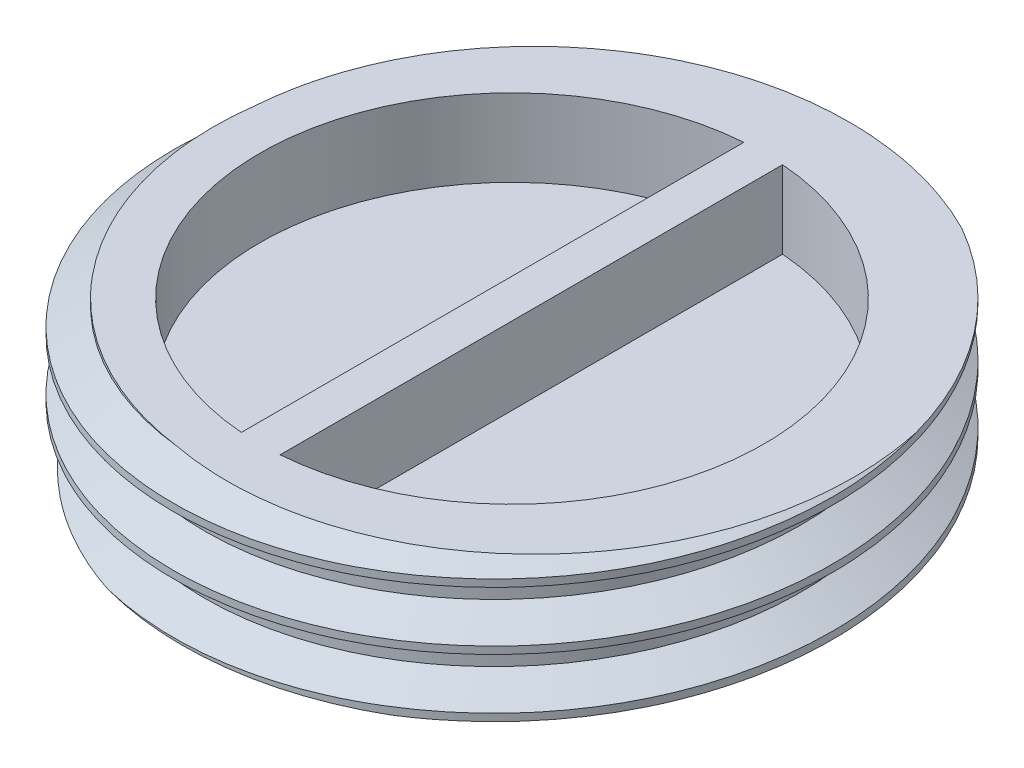
SolidWorks part; units mm, degrees
ref_plane "Front Plane" through (0, 0, 0) normal (0, 0, 1) x (1, 0, 0)
ref_plane "Top Plane" through (0, 0, 0) normal (0, 1, 0) x (1, 0, 0)
ref_plane "Right Plane" through (0, 0, 0) normal (1, 0, 0) x (0, 0, -1)
sketch "Sketch1" plane through (0, 0, 0) normal (0, 1, 0) x (1, 0, 0)
  circle A0 centre (0, 0) radius 8.5
extrude "Boss-Extrude1" add sketch "Sketch1" along normal blind 1.5
sketch "Sketch2" plane through (0, 1.5, 0) normal (0, 1, 0) x (1, 0, 0)
  line L1 (-0.5, 9.1092) -> (0.5, 9.1092)
  line L2 (-0.5, 9.1092) -> (-0.5, -9.1092)
  line L3 (-0.5, -9.1092) -> (0.5, -9.1092)
  line L4 (0.5, 9.1092) -> (0.5, -9.1092)
  line L5 (-0.5, 9.1092) -> (0.5, -9.1092) construction
  line L6 (-0.5, -9.1092) -> (0.5, 9.1092) construction
  line L8 (-11.5202, 0.5) -> (-11.5202, -0.5)
  circle A0 centre (0, 0) radius 8.5
  circle A1 centre (0, 0) radius 6.5
  circle M1 centre (0, 0) radius 8.5
extrude "Boss-Extrude2" add sketch "Sketch2" along normal blind 2 contours A1 L2 M1 | A1 L4 L2 M1 | A1 L4 M1 | L4 A1 L2 | A1 L2 L4 M1 region at (0, 1.5, -7.4943) region at (-0.6876, 1.5, -7.483) region at (6.0481, 1.5, -5.7022) region at (0, 1.5, 0) region at (0, 1.5, 7.4943)
thread "Thread3" pitch 1.5 method cut profile "Thread Profile3" start angle 0, offset 2, length 10, pitch 1.5, diameter 17
ref_plane "Plane3" through (-8.5, 5.5, 0) normal (0, 0, 1) x (-1, 0, 0)
sketch "Thread Profile3" plane through (-8.5, 5.5, 0) normal (0, 0, 1) x (-1, 0, 0)
  line L0 (0, 0) -> (0, 1.5) construction
  line L11 (0, 0) -> (0, 1.3125)
  line L12 (0, 1.3125) -> (-0.8119, 0.8437)
  line L13 (-0.8119, 0.8437) -> (-0.8119, 0.4687)
  line L15 (-0.8119, 0.4687) -> (0, 0)
  line L17 (-0.8119, 0.6562) -> (0, 0.6562) construction
  point P2 (0, 0)
  dimension "Pitch" = 1.5
  dimension "Profile_Angle" = 60
  dimension "Profile_Land" = 0.375
  dimension "Profile_Height" = 0.8119
